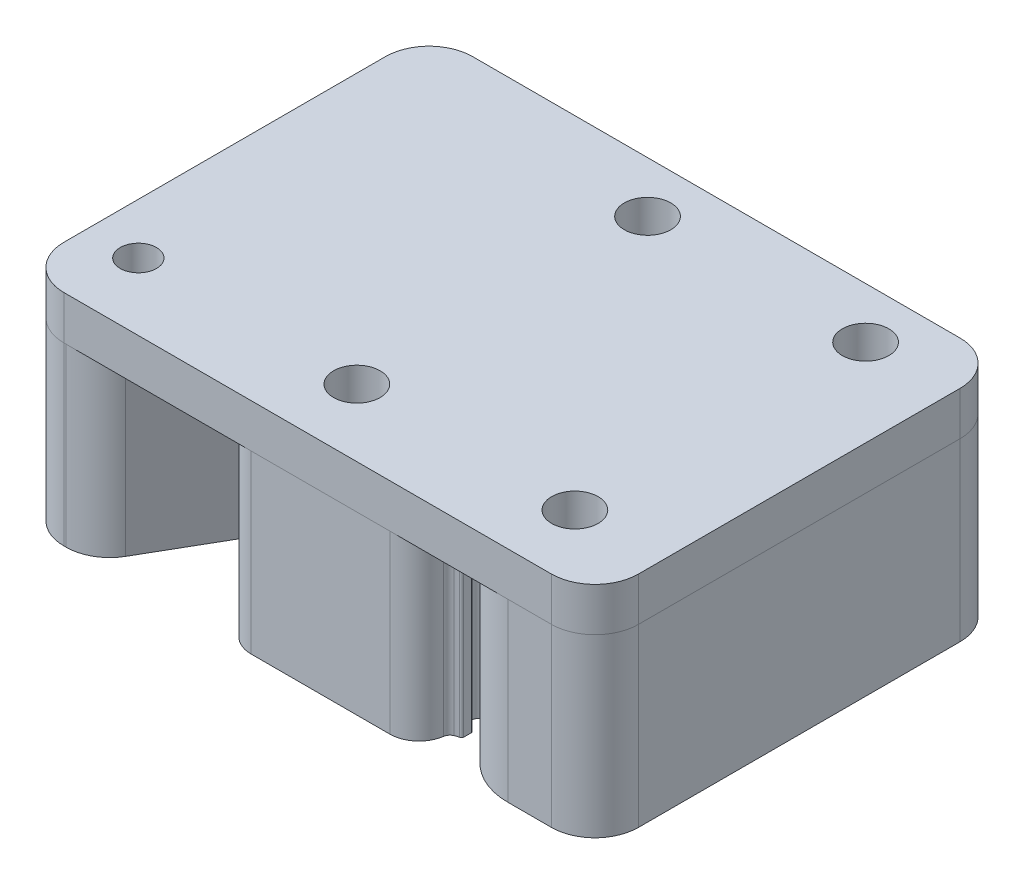
SolidWorks part; units mm, degrees
material "AISI 1045 Steel, cold drawn"
ref_plane "Front Plane" through (0, 0, 0) normal (0, 0, 1) x (1, 0, 0)
ref_plane "Top Plane" through (0, 0, 0) normal (0, 1, 0) x (1, 0, 0)
ref_plane "Right Plane" through (0, 0, 0) normal (1, 0, 0) x (0, 0, -1)
sketch "Sketch1" plane through (0, 0, 0) normal (0, 1, 0) x (1, 0, 0)
  line L0 (-13.5, -13.5) -> (-13.5, -14.619)
  line L1 (7.5, -10) -> (-7.5, -10) construction
  line L2 (7.5, -10) -> (7.5, 10) construction
  line L3 (7.5, 10) -> (-7.5, 10) construction
  line L4 (-7.5, -10) -> (-7.5, 10) construction
  line L5 (7.5, -10) -> (-7.5, 10) construction
  line L6 (7.5, 10) -> (-7.5, -10) construction
  line L7 (13.5, -13.5) -> (-13.5, -13.5) construction
  line L8 (13.5, -13.5) -> (13.5, 13.5)
  line L9 (13.5, 13.5) -> (-13.5, 13.5)
  line L10 (-13.5, -13.5) -> (-13.5, 13.5)
  line L11 (13.5, -13.5) -> (-13.5, 13.5) construction
  line L12 (13.5, 13.5) -> (-13.5, -13.5) construction
  line L13 (-13.5, -14.619) -> (13.5, -14.619)
  line L14 (13.5, -14.619) -> (13.5, -13.5)
  point P0 (0, 0)
  point P6 (0, 0)
  dimension "D1" = 15
  dimension "D2" = 27
  dimension "D3" = 1.119
  dimension "D4" = 20
extrude "Boss-Extrude1" add sketch "Sketch1" along normal mid plane 12.1
hole_wizard "M3 Clearance Hole1" positions "Sketch2" profile "Sketch3" hole size "M3" standard "ANSI Metric" end condition through all
sketch "Sketch2" plane through (0, 6.05, 0) normal (0, 1, 0) x (1, 0, 0)
  point P0 (-7.5, 10)
  point P3 (7.5, 10)
  point P6 (7.5, -10)
  point P9 (-7.5, -10)
sketch "Sketch3" plane through (-7.5, 6.05, -10) normal (1, 0, 0) x (0, 0, 1)
  line L0 (0, 0) -> (0, 12.1)
  line L1 (0, 12.1) -> (1.6, 12.1)
  line L2 (1.6, 12.1) -> (1.6, 0)
  line L5 (1.6, 0) -> (0, 0)
  line L11 (0, -6.35) -> (0, 107.95) construction
  dimension "Thru Hole Dia." = 3.2
  dimension "Thru Hole Depth" = 12.1
sketch "Sketch6" plane through (0, 6.05, 0) normal (0, 1, 0) x (1, 0, 0)
  line L0 (13.5, 13.5) -> (-13.5, 13.5) construction
  line L1 (-13.5, -14.619) -> (-28, -14.619)
  line L2 (-13.5, -14.619) -> (-13.5, 13.5)
  line L3 (-13.5, 13.5) -> (-28, 13.5)
  line L4 (-28, -14.619) -> (-28, 13.5)
  dimension "D1" = 28
extrude "Boss-Extrude3" add sketch "Sketch6" against normal up to surface (12.1 mm away) up to face at (-7.5, -6.05, -8.4)
sketch "Sketch8" plane through (0, 6.05, 0) normal (0, 1, 0) x (1, 0, 0)
  line L0 (-28, -14.619) -> (13.5, -14.619) construction
  line L2 (2.881, -10) -> (2.881, 4)
  line L3 (2.881, 4) -> (1.361, 4)
  line L4 (1.361, -14.619) -> (1.361, 4)
  line L5 (7.5, -14.619) -> (1.361, -14.619)
  arc A0 (2.881, -10) -> (7.5, -14.619) centre (7.5, -10) ccw
  dimension "D1" = 1.52
  dimension "D2" = 14
extrude "Cut-Extrude2" cut sketch "Sketch8" against normal up to surface (12.1 mm away) up to face at (-7.5, -6.05, -8.4)
sketch "Sketch9" plane through (0, 6.05, 0) normal (0, 1, 0) x (1, 0, 0)
  line L1 (2.881, 4) -> (6.306, 4)
  line L2 (2.881, 4) -> (2.881, -8)
  line L3 (2.881, -8) -> (6.306, -8)
  line L4 (6.306, 4) -> (6.306, -8)
  dimension "D1" = 3.425
  dimension "D2" = 12
extrude "Cut-Extrude3" cut sketch "Sketch9" against normal up to surface (12.1 mm away) up to face at (-7.5, -6.05, -8.4)
sketch "Sketch11" plane through (0, 6.05, 0) normal (0, 1, 0) x (1, 0, 0)
  line L1 (2.111, 0.7046) -> (2.111, 4.8734) construction
  line L4 (2.365, -998.8465) -> (2.365, 49001.1535) construction
  line L5 (2.111, 2.2598) -> (2.111, 2)
  line L6 (1.361, 3) -> (2.111, 3) construction
  line L7 (1.361, 4) -> (1.361, -14.619) construction
  line L8 (6.306, 4) -> (1.361, 4) construction
  line L9 (2.111, 2) -> (1.361, 2)
  line L10 (1.361, 2) -> (1.361, 4)
  line L11 (2.111, 4) -> (1.361, 4)
  line L12 (2.111, 3.7402) -> (2.111, 4)
  arc A2 (1.6728, 3.4989) -> (1.6728, 2.5011) centre (1.916, 3) ccw
  arc A4 (1.6728, 2.5011) -> (1.9806, 2.4085) centre (2.111, 3.4) ccw
  arc A5 (2.111, 2.2598) -> (1.9806, 2.4085) centre (1.961, 2.2598) ccw
  arc A6 (2.111, 3.7402) -> (1.9806, 3.5915) centre (1.961, 3.7402) cw
  arc A7 (1.6728, 3.4989) -> (1.9806, 3.5915) centre (2.111, 2.6) cw
  point P7 (1.361, 3)
  line M19 (1.361, -14.619) -> (1.361, 4)
  line M20 (1.361, 4) -> (6.306, 4)
  dimension "D3" = 0.555
  dimension "D4" = 1
  dimension "D5" = 1
  dimension "D6" = 0.15
  dimension "D1" = 0.254
  dimension "D2" = 0.75
  dimension "D7" = 1
extrude "Boss-Extrude4" add sketch "Sketch11" against normal up to surface (12.1 mm away) contours A2 A7 A6 L12 L10 M20 | L5 A5 A4 A2 L9 M19 region at (1.6833, 6.05, -3.7249) region at (1.6833, 6.05, -2.2751) up to face at (-7.5, -6.05, -8.4)
pattern_linear "LPattern1" count 9 spacing 2 along (0, 0, 1) of "Boss-Extrude4"
sketch "Sketch12" plane through (0, 6.05, 0) normal (0, 1, 0) x (1, 0, 0)
  circle A0 centre (2.111, 4) radius 0.5
  circle A1 centre (6.306, 4) radius 0.5
  circle A2 centre (6.306, -8) radius 0.5
  dimension "D1" = 1
extrude "Cut-Extrude5" cut sketch "Sketch12" against normal up to surface (12.1 mm away) up to face at (1.556, -6.05, 5.2005)
sketch "Sketch13" plane through (0, 6.05, 0) normal (0, 1, 0) x (1, 0, 0)
  line L3 (2.111, -14) -> (1.361, -14) construction
  line L4 (2.111, -13.7402) -> (2.111, -14) construction
  line L5 (2.111, -14) -> (1.361, -14)
  line L6 (2.111, -13.7402) -> (2.111, -14)
  line L7 (1.361, -14) -> (1.361, -13)
  arc A6 (1.6728, -12.5011) -> (1.6728, -13.4989) centre (1.916, -13) ccw construction
  arc A7 (1.6728, -13.4989) -> (1.9806, -13.5915) centre (2.111, -12.6) ccw construction
  arc A8 (2.111, -13.7402) -> (1.9806, -13.5915) centre (1.961, -13.7402) ccw construction
  arc A9 (1.361, -13) -> (1.6728, -13.4989) centre (1.916, -13) ccw
  arc A10 (1.6728, -13.4989) -> (1.9806, -13.5915) centre (2.111, -12.6) ccw
  arc A11 (2.111, -13.7402) -> (1.9806, -13.5915) centre (1.961, -13.7402) ccw
extrude "Cut-Extrude6" cut sketch "Sketch13" against normal up to surface (12.1 mm away) up to face at (1.6903, -6.05, 5.2284)
fillet "Fillet3" radius 0.5 7 edges at (5.806, 0, 8) (6.306, 0, 7.5) (5.806, 0, -4) (6.306, 0, -3.5) (2.611, 0, -4) (1.8595, 0, -3.5679) (2.881, 0, 8)
sketch "Sketch17" plane through (0, 6.05, 0) normal (0, 1, 0) x (1, 0, 0)
  line L0 (-21.1595, -14.619) -> (-15.513, -17.879)
  line L11 (-6.4019, 5.9019) -> (-3.8038, 4.4019) construction
  line L12 (-6.4019, 5.9019) -> (-2.9019, 11.9641) construction
  line L13 (-3.8038, 4.4019) -> (-0.3038, 10.4641) construction
  line L14 (-2.9019, 11.9641) -> (-0.3038, 10.4641) construction
  line L15 (-4.201, 12.7141) -> (0.9952, 9.7141) construction
  line L16 (-4.201, 12.7141) -> (-2.701, 15.3122) construction
  line L17 (0.9952, 9.7141) -> (2.4952, 12.3122) construction
  line L18 (-2.701, 15.3122) -> (2.4952, 12.3122) construction
  line L19 (-5.1029, 5.1519) -> (-0.1029, 13.8122) construction
  line L20 (-21.1595, -14.619) -> (-8.5843, 7.1619)
  line L21 (-15.513, -17.879) -> (-2.9378, 3.9019)
  line L22 (-8.5843, 7.1619) -> (-2.9378, 3.9019)
  line L23 (-22.5782, -10.8263) -> (-19.8719, -12.3888) construction
  line L24 (-22.5782, -10.8263) -> (-12.5782, 6.4942) construction
  line L25 (-19.8719, -12.3888) -> (-9.8719, 4.9317) construction
  line L26 (-12.5782, 6.4942) -> (-9.8719, 4.9317) construction
  line L27 (-28, -14.619) -> (1.361, -14.619) construction
  line L28 (-14.8719, -3.7285) -> (-17.5782, -2.166) construction
  circle A0 centre (-7.5, 10) radius 1.6 construction
  circle A1 centre (-7.5, -10) radius 1.6 construction
  dimension "D1" = 6.52
  dimension "D3" = 3
  dimension "D10" = 3
  dimension "D2" = 6
  dimension "D4" = 3
  dimension "D5" = 10
  dimension "D6" = 3.125
  dimension "D7" = 2.5
  dimension "D8" = 60
  dimension "D9" = 3
  dimension "D11" = 20
extrude "Cut-Extrude7" cut sketch "Sketch17" against normal up to surface (12.1 mm away) up to face at (1.9594, -6.05, 4.4571)
sketch "Sketch18" plane through (0, 6.05, 0) normal (0, 1, 0) x (1, 0, 0)
  line L0 (-26.0342, -14.619) -> (-26.0342, -10)
  line L2 (-14.1485, 10.3744) -> (-26.7237, -11.4065)
  line L3 (-12.344, 13.5) -> (-24.1063, -6.8729)
  line L4 (-12.344, 13.5) -> (-28, 13.5)
  line L5 (-28, 13.5) -> (-28, -14.619)
  line L7 (-28, -14.619) -> (-21.1595, -14.619) construction
  line L8 (-8.5843, 7.1619) -> (-21.1595, -14.619) construction
  line L10 (-28, -14.619) -> (-26.0342, -14.619)
  arc A2 (-24.1063, -6.8729) -> (-26.0342, -10) centre (-22.5342, -10) ccw
  point P0 (-7.5, -10)
  dimension "D2" = 3.5
  dimension "D1" = 6.425
extrude "Cut-Extrude8" cut sketch "Sketch18" against normal up to surface (12.1 mm away) contours A2 L10 | A2 L3 L4 L5 L10 region at (-22.8632, 6.05, -4.1187) up to face at (1.2277, -6.05, 4.4618)
hole_wizard "M3 Clearance Hole2" positions "Sketch19" profile "Sketch20" hole size "M3" standard "ANSI Metric" end condition up to next
sketch "Sketch19" plane through (0, 6.05, 0) normal (0, 1, 0) x (1, 0, 0)
  point P0 (-22.5342, -10)
sketch "Sketch20" plane through (-22.5342, 6.05, 10) normal (1, 0, 0) x (0, 0, 1)
  line L0 (0, 0) -> (0, 12.1)
  line L1 (0, 12.1) -> (1.6, 12.1)
  line L2 (1.6, 12.1) -> (1.6, 0)
  line L5 (1.6, 0) -> (0, 0)
  line L11 (0, -6.35) -> (0, 107.95) construction
  dimension "Thru Hole Dia." = 3.2
  dimension "Thru Hole Depth" = 12.1
fillet "Fillet4" radius 3 5 edges at (13.5, 0, 14.619) (13.5, 0, -13.5) (-12.344, 0, -13.5) (-26.0342, 0, 14.619) (-21.1595, 0, 14.619)
sketch "Sketch21" plane through (0, 6.05, 0) normal (0, 1, 0) x (1, 0, 0)
  line L0 (-8.5843, 7.1619) -> (-20.2935, -13.119) construction
  line L1 (-17.8343, -8.8595) -> (-20.8004, -7.147)
  line L2 (-17.8343, -8.8595) -> (-9.3343, 5.8629)
  line L3 (-20.8004, -7.147) -> (-12.3004, 7.5754)
  line L4 (-9.3343, 5.8629) -> (-12.3004, 7.5754)
  line L5 (-2.9378, 3.9019) -> (-8.5843, 7.1619) construction
  dimension "D3" = 17
  dimension "D1" = 3.425
  dimension "D2" = 1.5
extrude "Cut-Extrude9" cut sketch "Sketch21" against normal up to surface (12.1 mm away) up to face at (-22.5342, -6.05, 11.6)
sketch "Sketch22" plane through (0, 6.05, 0) normal (0, 1, 0) x (1, 0, 0)
  circle A0 centre (-20.8004, -7.147) radius 0.5
  circle A1 centre (-12.3004, 7.5754) radius 0.5
  circle A2 centre (-8.5843, 7.1619) radius 0.5
  circle A3 centre (-2.9378, 3.9019) radius 0.5
  arc A4 (2.544, 4.25) -> (1.6303, 3.8625) centre (2.111, 4) ccw construction
extrude "Cut-Extrude10" cut sketch "Sketch22" against normal up to surface (12.1 mm away) up to face at (-22.5342, -6.05, 11.6)
fillet "Fillet5" radius 0.5 10 edges at (-17.8343, 0, 8.8595) (-3.1878, 0, -3.4689) (-3.3708, 0, -4.1519) (-8.8343, 0, -6.7289) (-8.1513, 0, -6.9119) (-11.8674, 0, -7.3254) (-12.5504, 0, -7.1424) (-20.5504, 0, 6.714) (-20.3674, 0, 7.397) (-9.3343, 0, -5.8629)
ref_plane "Plane2" through (6.9551, 0, -12.0466) normal (0.5, 0, -0.866) x (-0.866, 0, -0.5)
hole_wizard "CBORE for M3 SHCS1" positions "Sketch23" profile "Sketch25" counterbore size "M3" standard "ANSI Metric" end condition up to next
sketch "Sketch23" plane through (6.9551, 0, -12.0466) normal (0.5, 0, -0.866) x (-0.866, 0, -0.5)
  line L0 (4.4952, -6.05) -> (9.4952, 6.05) construction
  line L1 (-2.3433, -6.05) -> (15.9402, -6.05) construction
  line L3 (-2.3433, 6.05) -> (15.9402, 6.05) construction
  point P15 (6.9952, 0)
  dimension "D1" = 5
sketch "Sketch25" plane through (0.8971, 0, -15.5442) normal (0, 1, 0) x (-0.866, 0, -0.5)
  line L0 (0, 0) -> (0, 12)
  line L1 (0, 12) -> (1.6, 12)
  line L3 (1.6, 12) -> (1.6, 6)
  line L4 (1.6, 6) -> (3.25, 6)
  line L5 (3.25, 6) -> (3.25, 0)
  line L7 (3.25, 0) -> (0, 0)
  line L11 (0, -6.35) -> (0, 107.95) construction
  dimension "Thru Hole Dia." = 3.2
  dimension "Thru Hole Depth" = 12
  dimension "C'Bore Dia." = 6.5
  dimension "C'Bore Depth" = 6
sketch "Sketch30" plane through (0, 6.05, 0) normal (0, 1, 0) x (1, 0, 0)
  line L1 (3.381, -8) -> (5.44, -8) construction
  line L2 (6.306, -7.134) -> (6.306, 3.134) construction
  line L3 (5.44, 4) -> (2.977, 4) construction
  line L4 (3.381, -8) -> (5.44, -8)
  line L5 (6.306, -7.134) -> (6.306, 3.134)
  line L6 (5.44, 4) -> (2.977, 4)
  line L7 (-18.0843, -9.2926) -> (-9.0843, 6.2959)
  line L8 (-20.0504, -7.5801) -> (-18.2673, -8.6095) construction
  line L9 (-12.7335, 6.8254) -> (-20.3674, -6.397) construction
  line L10 (-9.7673, 6.1129) -> (-11.5504, 7.1424) construction
  line L11 (-20.0504, -7.5801) -> (-18.2673, -8.6095)
  line L12 (-12.7335, 6.8254) -> (-20.3674, -6.397)
  line L13 (-9.7673, 6.1129) -> (-11.5504, 7.1424)
  line L14 (2.881, -8.5) -> (2.881, 4.0093)
  arc A0 (3.381, -8) -> (2.881, -8.5) centre (3.381, -8.5) ccw construction
  arc A1 (5.873, -8.25) -> (5.44, -8) centre (5.44, -8.5) ccw construction
  arc A2 (5.873, -8.25) -> (6.556, -7.567) centre (6.306, -8) ccw construction
  arc A3 (6.306, -7.134) -> (6.556, -7.567) centre (6.806, -7.134) ccw construction
  arc A4 (6.556, 3.567) -> (6.306, 3.134) centre (6.806, 3.134) ccw construction
  arc A5 (6.556, 3.567) -> (5.873, 4.25) centre (6.306, 4) ccw construction
  arc A6 (5.44, 4) -> (5.873, 4.25) centre (5.44, 4.5) ccw construction
  arc A7 (2.544, 4.25) -> (2.977, 4) centre (2.977, 4.5) ccw construction
  arc A8 (3.381, -8) -> (2.881, -8.5) centre (3.381, -8.5) ccw
  arc A9 (5.873, -8.25) -> (5.44, -8) centre (5.44, -8.5) ccw
  arc A10 (5.873, -8.25) -> (6.556, -7.567) centre (6.306, -8) ccw
  arc A11 (6.306, -7.134) -> (6.556, -7.567) centre (6.806, -7.134) ccw
  arc A12 (6.556, 3.567) -> (6.306, 3.134) centre (6.806, 3.134) ccw
  arc A13 (6.556, 3.567) -> (5.873, 4.25) centre (6.306, 4) ccw
  arc A14 (5.44, 4) -> (5.873, 4.25) centre (5.44, 4.5) ccw
  arc A15 (2.881, 4.0093) -> (2.977, 4) centre (2.977, 4.5) ccw
  arc A17 (-18.0843, -9.2926) -> (-18.2673, -8.6095) centre (-18.5173, -9.0426) ccw construction
  arc A18 (-20.0504, -7.5801) -> (-20.5504, -7.5801) centre (-20.3004, -8.0131) ccw construction
  arc A19 (-20.8004, -6.647) -> (-20.3674, -6.397) centre (-20.8004, -6.147) ccw construction
  arc A20 (-12.7335, 6.8254) -> (-12.7335, 7.3254) centre (-13.1665, 7.0754) ccw construction
  arc A21 (-11.8004, 7.5754) -> (-12.7335, 7.3254) centre (-12.3004, 7.5754) ccw construction
  arc A22 (-11.8004, 7.5754) -> (-11.5504, 7.1424) centre (-11.3004, 7.5754) ccw construction
  arc A23 (-9.7673, 6.1129) -> (-9.0843, 6.2959) centre (-9.5173, 6.5459) ccw construction
  arc A24 (-18.0843, -9.2926) -> (-18.2673, -8.6095) centre (-18.5173, -9.0426) ccw
  arc A25 (-20.0504, -7.5801) -> (-20.5504, -7.5801) centre (-20.3004, -8.0131) ccw
  arc A26 (-20.8004, -6.647) -> (-20.3674, -6.397) centre (-20.8004, -6.147) ccw
  arc A27 (-12.7335, 6.8254) -> (-12.7335, 7.3254) centre (-13.1665, 7.0754) ccw
  arc A28 (-11.8004, 7.5754) -> (-12.7335, 7.3254) centre (-12.3004, 7.5754) ccw
  arc A29 (-11.8004, 7.5754) -> (-11.5504, 7.1424) centre (-11.3004, 7.5754) ccw
  arc A30 (-9.7673, 6.1129) -> (-9.0843, 6.2959) centre (-9.5173, 6.5459) ccw
  arc A31 (-20.8004, -6.647) -> (-20.5504, -7.5801) centre (-20.8004, -7.147) ccw construction
  arc A32 (-20.8004, -6.647) -> (-20.5504, -7.5801) centre (-20.8004, -7.147) ccw
extrude "Boss-Extrude8" add sketch "Sketch30" against normal up to surface (12.1 mm away) up to face at (-22.5342, -6.05, 11.6)
fillet "Fillet6" radius 1 1 edges at (2.881, 0, -4.0093)
sketch "Sketch31" plane through (0, 6.05, 0) normal (0, 1, 0) x (1, 0, 0)
  line L0 (13.5, 6.9) -> (4.381, 6.9)
  line L2 (4.381, 6.9) -> (4.381, -6.9)
  line L3 (4.381, -6.9) -> (13.5, -6.9)
  line L4 (2.881, -10) -> (2.881, 3.4759) construction
  line L6 (13.5, 6.9) -> (13.5, -6.9)
  line L7 (13.5, -11.619) -> (13.5, 10.5) construction
  circle A0 centre (7.5, -10) radius 1.6 construction
  circle A1 centre (7.5, 10) radius 1.6 construction
  dimension "D1" = 3.1
  dimension "D2" = 3.1
  dimension "D3" = 1.5
extrude "Cut-Extrude11" cut sketch "Sketch31" against normal up to surface (12.1 mm away) up to face at (-0.8329, -6.05, 3.7569)
sketch "Sketch32" plane through (0, 6.05, 0) normal (0, 1, 0) x (1, 0, 0)
  line L0 (-10.0574, 7.6105) -> (-19.366, -8.5125)
  line L1 (-9.0173, 6.4119) -> (-20.2935, -13.119) construction
  line L2 (-13.21, 12) -> (-24.1063, -6.8729) construction
  line L3 (-13.21, 12) -> (-24.1063, -6.8729)
  line L5 (10.5, 13.5) -> (-10.6119, 13.5) construction
  line L6 (-7.5, 13.5) -> (-10.6119, 13.5)
  arc A0 (-19.366, -8.5125) -> (-24.1063, -6.8729) centre (-22.5342, -10) ccw
  arc A1 (-24.1063, -6.8729) -> (-26.0342, -10) centre (-22.5342, -10) ccw construction
  arc A2 (-7.5, 13.5) -> (-10.0574, 7.6105) centre (-7.5, 10) ccw
  arc A3 (-10.6119, 13.5) -> (-13.21, 12) centre (-10.6119, 10.5) ccw construction
  arc A4 (-10.6119, 13.5) -> (-13.21, 12) centre (-10.6119, 10.5) ccw
  dimension "D1" = 1.5
extrude "Cut-Extrude12" cut sketch "Sketch32" against normal up to surface (12.1 mm away) up to face at (-0.3561, -6.05, 3.5736)
sketch "Sketch34" plane through (0, -6.05, 0) normal (0, -1, 0) x (1, 0, 0)
  line L0 (0.111, -6.1826) -> (-7.4426, 6.9005)
  line L1 (-3.3708, -3.1519) -> (-13.6309, 14.619) construction
  line L2 (0.111, -6.1826) -> (0.111, 12.619)
  line L4 (0.111, 12.619) -> (-5.8414, 12.619)
  line L5 (2.111, 10.2598) -> (2.111, 9.7402) construction
  line L7 (-13.6309, 14.619) -> (1.361, 14.619) construction
  circle A2 centre (-7.5, 10) radius 3.1
  arc A3 (-7.4426, 6.9005) -> (-5.8414, 12.619) centre (-7.5, 10) ccw
  dimension "D2" = 1.5
  dimension "D3" = 2
  dimension "D4" = 2
  dimension "D1" = 1.5
extrude "Cut-Extrude14" cut sketch "Sketch34" against normal up to surface (12.1 mm away) up to face at (-0.2449, 6.05, 3.6119)
sketch "Sketch35" plane through (0, -6.05, 0) normal (0, -1, 0) x (1, 0, 0)
  line L0 (-4.9175, -11.9731) -> (0.7117, -8.7231) construction
  line L1 (-7.5622, -13.5) -> (1.2713, -8.4)
  line L2 (10.5, -13.5) -> (-7.5, -13.5) construction
  line L3 (1.2713, -8.4) -> (4.3871, -8.4)
  line L4 (7.5, -13.5) -> (-7.5622, -13.5)
  line L6 (4.381, -6.9) -> (13.5, -6.9) construction
  circle A1 centre (7.5, -10) radius 1.6 construction
  arc A3 (4.3871, -8.4) -> (7.5, -13.5) centre (7.5, -10) ccw
  dimension "D1" = 1.5
extrude "Cut-Extrude15" cut sketch "Sketch35" against normal up to surface (12.1 mm away) up to face at (-2.7337, 6.05, 6.3401)
fillet "Fillet7" radius 2 9 edges at (-13.6309, 0, 14.619) (1.361, 0, 14.619) (13.5, 0, 6.9) (4.381, 0, 6.9) (13.5, 0, -6.9) (4.381, 0, -6.9) (-19.366, 0, 8.5125) (-7.5612, 0, -13.4995) (-10.0574, 0, -7.6105)
fillet "Fillet8" radius 1 6 edges at (0.111, 0, 12.619) (0.111, 0, -6.1826) (-5.8414, 0, 12.619) (-7.4426, 0, 6.9005) (4.3871, 0, -8.4) (1.2713, 0, -8.4)
sketch "Sketch36" plane through (0, 6.05, 0) normal (0, 1, 0) x (1, 0, 0)
  line L0 (2.881, 4.4759) -> (2.881, 3.4759)
  line L1 (1.611, 4) -> (1.611, 4.4759)
  arc A0 (1.611, 4.4759) -> (2.881, 4.4759) centre (2.246, 4.4759) cw
  arc A3 (2.544, 4.25) -> (1.6303, 3.8625) centre (2.111, 4) ccw construction
  arc A4 (2.544, 4.25) -> (2.6117, 4.1586) centre (2.977, 4.5) ccw construction
  arc A5 (2.881, 3.4759) -> (2.6117, 4.1586) centre (1.881, 3.4759) ccw construction
  arc A6 (2.544, 4.25) -> (1.611, 4) centre (2.111, 4) ccw
  arc A7 (2.544, 4.25) -> (2.6117, 4.1586) centre (2.977, 4.5) ccw
  arc A8 (2.881, 3.4759) -> (2.6117, 4.1586) centre (1.881, 3.4759) ccw
  dimension "D1" = 1
extrude "Cut-Extrude16" cut sketch "Sketch36" against normal up to surface (12.1 mm away) up to face at (-2.9137, -6.05, 6.8822)
sketch "Sketch37" plane through (0, 6.05, 0) normal (0, 1, 0) x (1, 0, 0)
  line L0 (-10.6817, 6.5291) -> (-9.847, 7.9748)
  line L1 (-18.0522, -6.2369) -> (-10.6817, 6.5291) construction
  line L2 (1.0392, 8.534) -> (-6.9682, 13.1571) construction
  line L3 (-6.6764, 12.9886) -> (-6.9682, 13.1571)
  arc A0 (-6.6764, 12.9886) -> (-9.847, 7.9748) centre (-7.5, 10) ccw
  circle A1 centre (-7.5, 10) radius 1.6 construction
  arc A2 (-6.9682, 13.1571) -> (-8.5926, 13.3251) centre (-7.9682, 11.425) ccw construction
  arc A3 (-8.5926, 13.3251) -> (-10.6269, 8.4276) centre (-7.5, 10) ccw construction
  arc A4 (-10.6817, 6.5291) -> (-10.6269, 8.4276) centre (-12.4137, 7.5291) ccw construction
  arc A5 (-6.9682, 13.1571) -> (-8.5926, 13.3251) centre (-7.9682, 11.425) ccw
  arc A6 (-8.5926, 13.3251) -> (-10.6269, 8.4276) centre (-7.5, 10) ccw
  arc A7 (-10.6817, 6.5291) -> (-10.6269, 8.4276) centre (-12.4137, 7.5291) ccw
  dimension "D1" = 1.5
extrude "Cut-Extrude17" cut sketch "Sketch37" against normal up to surface (12.1 mm away) up to face at (-2.9137, -6.05, 6.8822)
fillet "Fillet9" radius 2 2 edges at (-6.6764, 0, -12.9886) (-9.847, 0, -7.9748)
sketch "Sketch38" plane through (0, 6.05, 0) normal (0, 1, 0) x (1, 0, 0)
  line L0 (-26.0342, -10) -> (-26.0342, 13.1)
  line L1 (-26.0342, 13.1) -> (-7.5, 13.1)
  line L2 (-24.5342, -7.1277) -> (-24.5342, 11.6)
  line L3 (-24.5342, 11.6) -> (-10.1552, 11.6)
  line L4 (-24.5342, -10) -> (-24.5342, 11.6) construction
  line L5 (-24.5342, 11.6) -> (-7.5, 11.6) construction
  arc A0 (-7.2093, 13.0863) -> (-10.3388, 8.7545) centre (-7.5, 10) ccw construction
  arc A1 (-7.5, 13.1) -> (-10.1552, 11.6) centre (-7.5, 10) ccw
  arc A2 (-20.7842, -6.9689) -> (-26.0342, -10) centre (-22.5342, -10) ccw construction
  arc A3 (-24.5342, -7.1277) -> (-26.0342, -10) centre (-22.5342, -10) ccw
  dimension "D1" = 1.5
extrude "Boss-Extrude9" add sketch "Sketch38" against normal up to surface (12.1 mm away) up to face at (-2.9137, -6.05, 6.8822)
fillet "Fillet10" radius 2 4 edges at (-24.5342, 0, 7.1277) (-10.1552, 0, -11.6) (-26.0342, 0, -13.1) (-24.5342, 0, -11.6)
sketch "Sketch39" plane through (0.9551, 0, -1.6543) normal (-0.5, 0, 0.866) x (0.866, 0, 0.5)
  circle A0 centre (-6.9952, 0) radius 1.6 construction
  circle A1 centre (-6.9952, 0) radius 1.6
extrude "Boss-Extrude10" add sketch "Sketch39" against normal up to surface (6 mm away)
sketch "Sketch40" plane through (0, 6.05, 0) normal (0, 1, 0) x (1, 0, 0)
  line L0 (-22.5342, 11.6) -> (-12.5843, 11.6) construction
  line L1 (-24.5342, -4.5) -> (-24.5342, 9.6) construction
  line L2 (-18.0522, -6.2369) -> (-10.4382, 6.9509) construction
  line L3 (-22.5342, 11.6) -> (-12.5843, 11.6)
  line L4 (-24.5342, -4.5) -> (-24.5342, 9.6)
  line L5 (-18.0522, -6.2369) -> (-10.4382, 6.9509)
  line L6 (0.111, 2.4506) -> (0.111, -11.619) construction
  line L7 (-0.889, -12.619) -> (-3.7332, -12.619) construction
  line L8 (-6.7643, -5.7258) -> (-1.755, 2.9506) construction
  line L9 (0.111, 2.4506) -> (0.111, -11.619)
  line L10 (-0.889, -12.619) -> (-3.7332, -12.619)
  line L11 (-6.7643, -5.7258) -> (-1.755, 2.9506)
  line L12 (6.381, -6.9) -> (11.5, -6.9) construction
  line L13 (4.381, 4.9) -> (4.381, -4.9) construction
  line L14 (11.5, 6.9) -> (6.381, 6.9) construction
  line L15 (6.381, -6.9) -> (11.5, -6.9)
  line L16 (4.381, 4.9) -> (4.381, -4.9)
  line L17 (11.5, 6.9) -> (6.381, 6.9)
  line L18 (13.5, 8.9) -> (13.5, -8.9)
  arc A0 (-10.4382, 6.9509) -> (-10.3388, 8.7545) centre (-12.1702, 7.9509) ccw construction
  arc A1 (-10.5905, 9.7569) -> (-10.3388, 8.7545) centre (-7.5, 10) ccw construction
  arc A2 (-10.5905, 9.7569) -> (-12.5843, 11.6) centre (-12.5843, 9.6) ccw construction
  arc A3 (-22.5342, 11.6) -> (-24.5342, 9.6) centre (-22.5342, 9.6) ccw construction
  arc A4 (-24.5342, -4.5) -> (-22.5342, -6.5) centre (-22.5342, -4.5) ccw construction
  arc A5 (-20.7842, -6.9689) -> (-22.5342, -6.5) centre (-22.5342, -10) ccw construction
  arc A6 (-20.7842, -6.9689) -> (-18.0522, -6.2369) centre (-19.7842, -5.2369) ccw construction
  arc A7 (-10.4382, 6.9509) -> (-10.3388, 8.7545) centre (-12.1702, 7.9509) ccw
  arc A8 (-10.5905, 9.7569) -> (-10.3388, 8.7545) centre (-7.5, 10) ccw
  arc A9 (-10.5905, 9.7569) -> (-12.5843, 11.6) centre (-12.5843, 9.6) ccw
  arc A10 (-22.5342, 11.6) -> (-24.5342, 9.6) centre (-22.5342, 9.6) ccw
  arc A11 (-24.5342, -4.5) -> (-22.5342, -6.5) centre (-22.5342, -4.5) ccw
  arc A12 (-20.7842, -6.9689) -> (-22.5342, -6.5) centre (-22.5342, -10) ccw
  arc A13 (-20.7842, -6.9689) -> (-18.0522, -6.2369) centre (-19.7842, -5.2369) ccw
  arc A14 (0.111, 2.4506) -> (-1.755, 2.9506) centre (-0.889, 2.4506) ccw construction
  arc A15 (-0.889, -12.619) -> (0.111, -11.619) centre (-0.889, -11.619) ccw construction
  arc A16 (-4.6519, -11.2241) -> (-3.7332, -12.619) centre (-3.7332, -11.619) ccw construction
  arc A17 (-4.6519, -11.2241) -> (-6.289, -7.1463) centre (-7.5, -10) ccw construction
  arc A18 (-6.7643, -5.7258) -> (-6.289, -7.1463) centre (-5.8983, -6.2258) ccw construction
  arc A19 (0.111, 2.4506) -> (-1.755, 2.9506) centre (-0.889, 2.4506) ccw
  arc A20 (-0.889, -12.619) -> (0.111, -11.619) centre (-0.889, -11.619) ccw
  arc A21 (-4.6519, -11.2241) -> (-3.7332, -12.619) centre (-3.7332, -11.619) ccw
  arc A22 (-4.6519, -11.2241) -> (-6.289, -7.1463) centre (-7.5, -10) ccw
  arc A23 (-6.7643, -5.7258) -> (-6.289, -7.1463) centre (-5.8983, -6.2258) ccw
  arc A24 (13.5, -8.9) -> (11.5, -6.9) centre (11.5, -8.9) ccw construction
  arc A25 (4.381, -4.9) -> (6.381, -6.9) centre (6.381, -4.9) ccw construction
  arc A26 (6.381, 6.9) -> (4.381, 4.9) centre (6.381, 4.9) ccw construction
  arc A27 (11.5, 6.9) -> (13.5, 8.9) centre (11.5, 8.9) ccw construction
  arc A28 (13.5, -8.9) -> (11.5, -6.9) centre (11.5, -8.9) ccw
  arc A29 (4.381, -4.9) -> (6.381, -6.9) centre (6.381, -4.9) ccw
  arc A30 (6.381, 6.9) -> (4.381, 4.9) centre (6.381, 4.9) ccw
  arc A31 (11.5, 6.9) -> (13.5, 8.9) centre (11.5, 8.9) ccw
extrude "Boss-Extrude11" add sketch "Sketch40" against normal up to surface (12.1 mm away) up to face at (-17.7037, -6.05, -3.3974)
sketch "Sketch41" plane through (0, 6.05, 0) normal (0, 1, 0) x (1, 0, 0)
  line L0 (10.5, 13.5) -> (-23.0342, 13.5)
  line L22 (13.5, -11.619) -> (13.5, 10.5)
  line L23 (10.5, 13.5) -> (7.5, 13.5)
  line L24 (3.0402, 8.4) -> (1.5392, 8.4)
  line L25 (1.0392, 8.534) -> (-6.3969, 12.8272)
  line L26 (-7.5, 13.1) -> (-24.0342, 13.1)
  line L27 (-26.0342, 11.1) -> (-26.0342, -11.619)
  line L28 (-23.0342, -14.619) -> (-22.8916, -14.619)
  line L29 (-20.2935, -13.119) -> (-9.0173, 6.4119)
  line L30 (-7.8343, 6.7289) -> (-3.6878, 4.3349)
  line L31 (-3.3708, 3.1519) -> (-11.8988, -11.619)
  line L32 (-10.1668, -14.619) -> (-0.6104, -14.619)
  line L33 (2.111, -12.2598) -> (2.111, -11.7402)
  line L34 (2.111, -10.2598) -> (2.111, -9.7402)
  line L35 (2.111, -8.2598) -> (2.111, -7.7402)
  line L36 (2.111, -6.2598) -> (2.111, -5.7402)
  line L37 (2.111, -4.2598) -> (2.111, -3.7402)
  line L38 (2.111, -2.2598) -> (2.111, -1.7402)
  line L39 (2.111, -0.2598) -> (2.111, 0.2598)
  line L40 (2.111, 1.7402) -> (2.111, 2.2598)
  line L41 (1.611, 4) -> (1.611, 4.4759)
  line L42 (2.881, 4.4759) -> (2.881, -10)
  line L43 (7.5, -14.619) -> (10.5, -14.619)
  line L44 (13.5, -11.619) -> (13.5, 10.5)
  line L49 (-26.0342, 10.5) -> (-26.0342, -11.619)
  line L50 (-23.0342, -14.619) -> (-22.8916, -14.619)
  line L65 (-22.8916, -14.619) -> (10.5, -14.619)
  circle A2 centre (7.5, 10) radius 1.6 construction
  circle A3 centre (-7.5, 10) radius 1.6 construction
  circle A6 centre (7.5, 10) radius 1.6
  circle A7 centre (-7.5, 10) radius 1.6
  circle A8 centre (7.5, -10) radius 1.6 construction
  circle A9 centre (7.5, -10) radius 1.6
  circle A10 centre (-7.5, -10) radius 1.6 construction
  circle A11 centre (-7.5, -10) radius 1.6
  arc A12 (-23.0342, 13.5) -> (-26.0342, 10.5) centre (-23.0342, 10.5) ccw
  circle A13 centre (-22.5342, -10) radius 1.25
  arc A63 (13.5, 10.5) -> (10.5, 13.5) centre (10.5, 10.5) ccw
  arc A64 (7.5, 13.5) -> (4.0313, 9.5333) centre (7.5, 10) ccw
  arc A65 (3.0402, 8.4) -> (4.0313, 9.5333) centre (3.0402, 9.4) ccw
  arc A66 (1.0392, 8.534) -> (1.5392, 8.4) centre (1.5392, 9.4) ccw
  arc A67 (-6.3969, 12.8272) -> (-7.2093, 13.0863) centre (-7.3969, 11.0952) ccw
  arc A68 (-7.2093, 13.0863) -> (-7.5, 13.1) centre (-7.5, 10) ccw
  arc A69 (-24.0342, 13.1) -> (-26.0342, 11.1) centre (-24.0342, 11.1) ccw
  arc A70 (-26.0342, -11.619) -> (-23.0342, -14.619) centre (-23.0342, -11.619) ccw
  arc A71 (-22.8916, -14.619) -> (-20.2935, -13.119) centre (-22.8916, -11.619) ccw
  arc A72 (-9.0173, 6.4119) -> (-9.0173, 6.9119) centre (-9.4503, 6.6619) ccw
  arc A73 (-8.0843, 7.1619) -> (-9.0173, 6.9119) centre (-8.5843, 7.1619) ccw
  arc A74 (-8.0843, 7.1619) -> (-7.8343, 6.7289) centre (-7.5843, 7.1619) ccw
  arc A75 (-3.6878, 4.3349) -> (-3.1878, 4.3349) centre (-3.4378, 4.7679) ccw
  arc A76 (-2.9378, 3.4019) -> (-3.1878, 4.3349) centre (-2.9378, 3.9019) ccw
  arc A77 (-2.9378, 3.4019) -> (-3.3708, 3.1519) centre (-2.9378, 2.9019) ccw
  arc A78 (-11.8988, -11.619) -> (-10.1668, -14.619) centre (-10.1668, -12.619) ccw
  arc A79 (-0.6104, -14.619) -> (1.3672, -12.9172) centre (-0.6104, -12.619) ccw
  arc A80 (1.6728, -12.5011) -> (1.3672, -12.9172) centre (1.916, -13) ccw
  arc A81 (1.9806, -12.4085) -> (1.6728, -12.5011) centre (2.111, -13.4) ccw
  arc A82 (1.9806, -12.4085) -> (2.111, -12.2598) centre (1.961, -12.2598) ccw
  arc A83 (2.111, -11.7402) -> (1.9806, -11.5915) centre (1.961, -11.7402) ccw
  arc A84 (1.6728, -11.4989) -> (1.9806, -11.5915) centre (2.111, -10.6) ccw
  arc A85 (1.6728, -10.5011) -> (1.6728, -11.4989) centre (1.916, -11) ccw
  arc A86 (1.9806, -10.4085) -> (1.6728, -10.5011) centre (2.111, -11.4) ccw
  arc A87 (1.9806, -10.4085) -> (2.111, -10.2598) centre (1.961, -10.2598) ccw
  arc A88 (2.111, -9.7402) -> (1.9806, -9.5915) centre (1.961, -9.7402) ccw
  arc A89 (1.6728, -9.4989) -> (1.9806, -9.5915) centre (2.111, -8.6) ccw
  arc A90 (1.6728, -8.5011) -> (1.6728, -9.4989) centre (1.916, -9) ccw
  arc A91 (1.9806, -8.4085) -> (1.6728, -8.5011) centre (2.111, -9.4) ccw
  arc A92 (1.9806, -8.4085) -> (2.111, -8.2598) centre (1.961, -8.2598) ccw
  arc A93 (2.111, -7.7402) -> (1.9806, -7.5915) centre (1.961, -7.7402) ccw
  arc A94 (1.6728, -7.4989) -> (1.9806, -7.5915) centre (2.111, -6.6) ccw
  arc A95 (1.6728, -6.5011) -> (1.6728, -7.4989) centre (1.916, -7) ccw
  arc A96 (1.9806, -6.4085) -> (1.6728, -6.5011) centre (2.111, -7.4) ccw
  arc A97 (1.9806, -6.4085) -> (2.111, -6.2598) centre (1.961, -6.2598) ccw
  arc A98 (2.111, -5.7402) -> (1.9806, -5.5915) centre (1.961, -5.7402) ccw
  arc A99 (1.6728, -5.4989) -> (1.9806, -5.5915) centre (2.111, -4.6) ccw
  arc A100 (1.6728, -4.5011) -> (1.6728, -5.4989) centre (1.916, -5) ccw
  arc A101 (1.9806, -4.4085) -> (1.6728, -4.5011) centre (2.111, -5.4) ccw
  arc A102 (1.9806, -4.4085) -> (2.111, -4.2598) centre (1.961, -4.2598) ccw
  arc A103 (2.111, -3.7402) -> (1.9806, -3.5915) centre (1.961, -3.7402) ccw
  arc A104 (1.6728, -3.4989) -> (1.9806, -3.5915) centre (2.111, -2.6) ccw
  arc A105 (1.6728, -2.5011) -> (1.6728, -3.4989) centre (1.916, -3) ccw
  arc A106 (1.9806, -2.4085) -> (1.6728, -2.5011) centre (2.111, -3.4) ccw
  arc A107 (1.9806, -2.4085) -> (2.111, -2.2598) centre (1.961, -2.2598) ccw
  arc A108 (2.111, -1.7402) -> (1.9806, -1.5915) centre (1.961, -1.7402) ccw
  arc A109 (1.6728, -1.4989) -> (1.9806, -1.5915) centre (2.111, -0.6) ccw
  arc A110 (1.6728, -0.5011) -> (1.6728, -1.4989) centre (1.916, -1) ccw
  arc A111 (1.9806, -0.4085) -> (1.6728, -0.5011) centre (2.111, -1.4) ccw
  arc A112 (1.9806, -0.4085) -> (2.111, -0.2598) centre (1.961, -0.2598) ccw
  arc A113 (2.111, 0.2598) -> (1.9806, 0.4085) centre (1.961, 0.2598) ccw
  arc A114 (1.6728, 0.5011) -> (1.9806, 0.4085) centre (2.111, 1.4) ccw
  arc A115 (1.6728, 1.4989) -> (1.6728, 0.5011) centre (1.916, 1) ccw
  arc A116 (1.9806, 1.5915) -> (1.6728, 1.4989) centre (2.111, 0.6) ccw
  arc A117 (1.9806, 1.5915) -> (2.111, 1.7402) centre (1.961, 1.7402) ccw
  arc A118 (2.111, 2.2598) -> (1.9806, 2.4085) centre (1.961, 2.2598) ccw
  arc A119 (1.6728, 2.5011) -> (1.9806, 2.4085) centre (2.111, 3.4) ccw
  arc A120 (1.5128, 3.3814) -> (1.6728, 2.5011) centre (1.916, 3) ccw
  arc A121 (1.5128, 3.3814) -> (1.6303, 3.8625) centre (1.1496, 3.725) ccw
  arc A122 (1.611, 4) -> (1.6303, 3.8625) centre (2.111, 4) ccw
  arc A123 (2.881, 4.4759) -> (1.611, 4.4759) centre (2.246, 4.4759) ccw
  arc A124 (2.881, -10) -> (7.5, -14.619) centre (7.5, -10) ccw
  arc A125 (10.5, -14.619) -> (13.5, -11.619) centre (10.5, -11.619) ccw
  arc A126 (13.5, 10.5) -> (10.5, 13.5) centre (10.5, 10.5) ccw
  arc A133 (-26.0342, -11.619) -> (-23.0342, -14.619) centre (-23.0342, -11.619) ccw
  arc A188 (10.5, -14.619) -> (13.5, -11.619) centre (10.5, -11.619) ccw
  dimension "D2" = 3
  dimension "D3" = 2.5
  dimension "D1" = 0
extrude "Boss-Extrude12" add sketch "Sketch41" along normal blind 3 separate body
